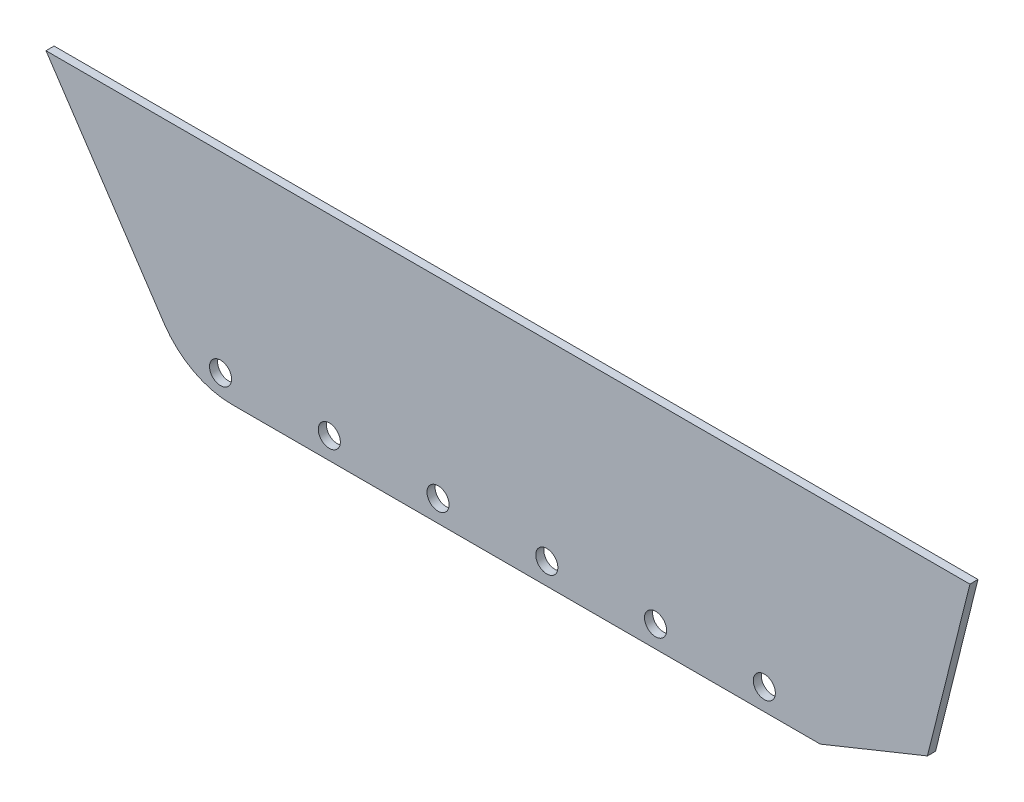
SolidWorks part; units mm, degrees
material "5052-H34"
ref_plane "Front Plane" through (0, 0, 0) normal (0, 0, 1) x (1, 0, 0)
ref_plane "Top Plane" through (0, 0, 0) normal (0, 1, 0) x (1, 0, 0)
ref_plane "Right Plane" through (0, 0, 0) normal (1, 0, 0) x (0, 0, -1)
sketch "Sketch1" plane through (0, 0, 0) normal (0, 0, 1) x (1, 0, 0)
  line L3 (428.1206, 28.9396) -> (0.5404, 28.9396)
  line L6 (-98.8794, 3.851) -> (-31.8794, -96.649)
  line L7 (428.1206, 28.9396) -> (403.1206, -71.149)
  line L9 (403.1206, -71.149) -> (366, -96.649)
  line L10 (-31.8794, -96.649) -> (366, -96.649)
  line L11 (0.5404, 28.9396) -> (-115.6052, 28.9396)
  line L12 (-98.8794, 3.851) -> (-115.6052, 28.9396)
  circle A0 centre (-12.8794, -83.899) radius 6.5
  circle A1 centre (51.1206, -83.899) radius 6.5
  circle A2 centre (115.1206, -83.899) radius 6.5
  circle A3 centre (179.1206, -83.899) radius 6.5
  circle A4 centre (243.1206, -83.899) radius 6.5
  circle A5 centre (307.1206, -83.899) radius 6.5
  point P0 (-48.8794, -71.149)
  point P2 (-31.8794, -96.649)
  point P8 (48, -83.899)
  point P9 (403.1206, -71.149)
  dimension "D2" = 64
  dimension "D4" = 64
  dimension "D1" = 25.5
  dimension "D3" = 75
  dimension "D5" = 25
  dimension "D6" = 96
  dimension "D7" = 527
  dimension "D8" = 180
  dimension "D9" = 64
  dimension "D10" = 64
  dimension "D11" = 64
  dimension "D12" = 123.69
  dimension "D13" = 12.75
extrude "Boss-Extrude1" add sketch "Sketch1" along normal blind 4.7625 contours L3 L11 L12 L6 L10 L9 L7
extrude "Cut-Extrude1" cut sketch "Sketch1<4>" along normal through all contours A0 | A1 | A2 | A3 | A4 | A5 region at (-12.8794, -83.899, 0)
sketch "Sketch1<4>" plane through (0, 0, 0) normal (0, 0, 1) x (1, 0, 0) same geometry as "Sketch1"
sketch "Sketch2" plane through (0, 0, 0) normal (0, 0, -1) x (-1, 0, 0)
  circle A0 centre (-275.1206, -83.899) radius 6.5
  circle A2 centre (-233.5603, -132.5687) radius 6.5
  circle A3 centre (-192, -83.899) radius 6.5
  circle A4 centre (-128, -83.899) radius 6.5
  circle A5 centre (-64, -83.899) radius 6.5
  circle A6 centre (0, -83.899) radius 6.5
  dimension "D2" = 0
  dimension "D3" = 64
  dimension "D4" = 64
  dimension "D5" = 64
  dimension "D6" = 64
  dimension "D7" = 64
  dimension "D1" = 32
sketch "Sketch5" plane through (0, 0, 0) normal (0, 0, -1) x (-1, 0, 0)
  line L0 (48.8794, -71.149) -> (-14.2353, -96.649)
  line L1 (31.8794, -96.649) -> (-366, -96.649) construction
  line L2 (-14.2353, -96.649) -> (31.8794, -96.649)
  line L3 (31.8794, -96.649) -> (48.8794, -71.149)
  line L6 (-366, -96.649) -> (-403.1206, -71.149)
  line L7 (-403.1206, -71.149) -> (-352, -71.149)
  line L9 (-352, -71.149) -> (-326.5, -96.649)
  line L11 (-366, -96.649) -> (-326.5, -96.649)
  dimension "D1" = 22
  dimension "D2" = 45
extrude "Cut-Extrude2" [suppressed] cut sketch "Sketch5" against normal up to next
sketch "Sketch6" plane through (0, 0, 4.7625) normal (0, 0, 1) x (1, 0, 0)
  line L0 (-48.8794, -71.149) -> (14.2353, -96.649)
  line L1 (-31.8794, -96.649) -> (366, -96.649) construction
  line L2 (14.2353, -96.649) -> (-31.8794, -96.649)
  line L3 (-31.8794, -96.649) -> (-48.8794, -71.149)
  dimension "D1" = 158
fillet "Fillet1" radius 48 1 edges at (-31.8794, -96.649, 2.3813)
sketch "Sketch7" plane through (0, 0, 4.7625) normal (0, 0, 1) x (1, 0, 0)
  line L0 (403.1206, -71.149) -> (340.0059, -96.649)
  line L1 (-31.8794, -96.649) -> (366, -96.649) construction
  line L2 (340.0059, -96.649) -> (366, -96.649)
  line L3 (366, -96.649) -> (403.1206, -71.149)
  dimension "D1" = 22
extrude "Cut-Extrude3" cut sketch "Sketch7" against normal blind 10
sketch "Sketch9" plane through (0, 0, 0) normal (0, 0, -1) x (-1, 0, 0)
  line L0 (-403.1206, -71.149) -> (48.8794, -71.149)
  line L1 (48.8794, -71.149) -> (48.8794, -114.9143)
  line L2 (48.8794, -114.9143) -> (-403.1206, -114.9143)
  line L3 (-403.1206, -114.9143) -> (-403.1206, -71.149)
extrude "Cut-Extrude4" [suppressed] cut sketch "Sketch9" against normal blind 10
